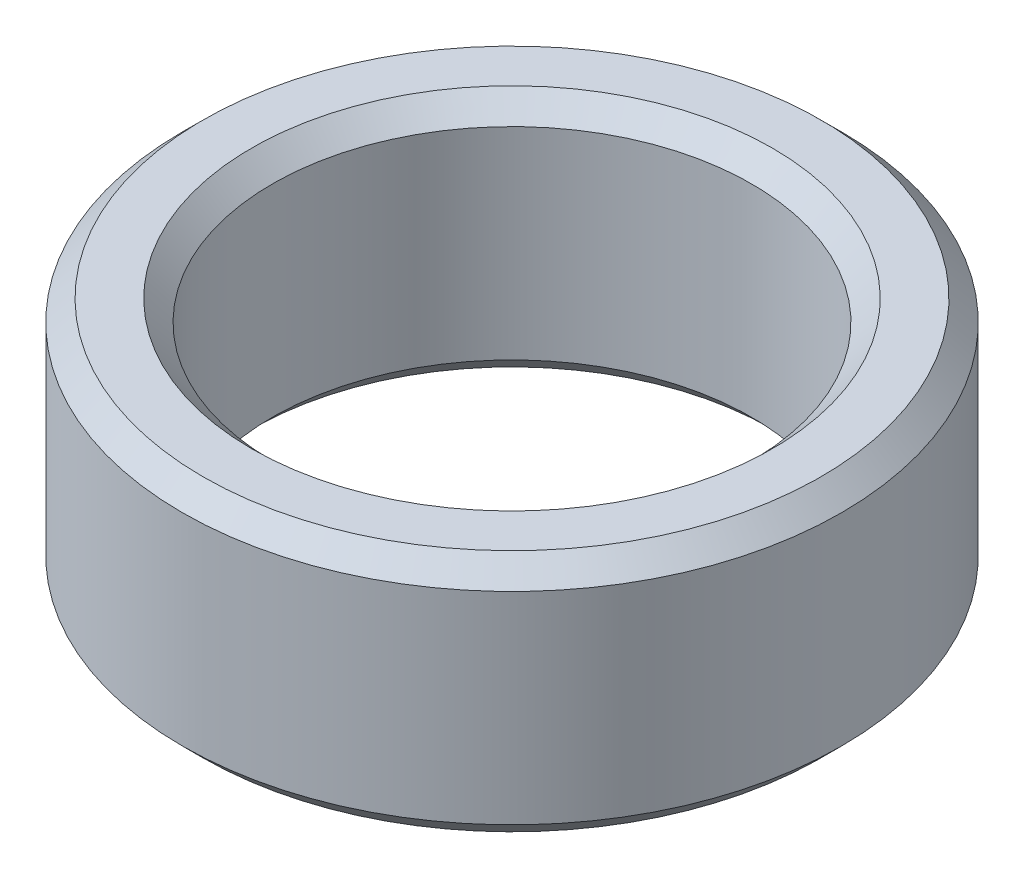
SolidWorks part; units mm, degrees
ref_plane "Front Plane" through (0, 0, 0) normal (0, 0, 1) x (1, 0, 0)
ref_plane "Top Plane" through (0, 0, 0) normal (0, 1, 0) x (1, 0, 0)
ref_plane "Right Plane" through (0, 0, 0) normal (1, 0, 0) x (0, 0, -1)
sketch "Sketch1" plane through (0, 0, 0) normal (0, 1, 0) x (1, 0, 0)
  circle A0 centre (0, 0) radius 37.5
  dimension "SLEEVE_OD" = 75
extrude "Boss-Extrude1" add sketch "Sketch1" along normal blind 27.6922
sketch "Sketch2" plane through (0, 0, 0) normal (0, 1, 0) x (1, 0, 0)
  circle A0 centre (0, 0) radius 27.2636
  dimension "BORE_D" = 54.5271
extrude "Cut-Extrude1" cut sketch "Sketch2" along normal through all
chamfer "Chamfer1" distance 2.3543 angle 45 4 edges at (0, 27.6922, 27.2636) (0, 0, 27.2636) (0, 0, 37.5) (0, 27.6922, 37.5)
